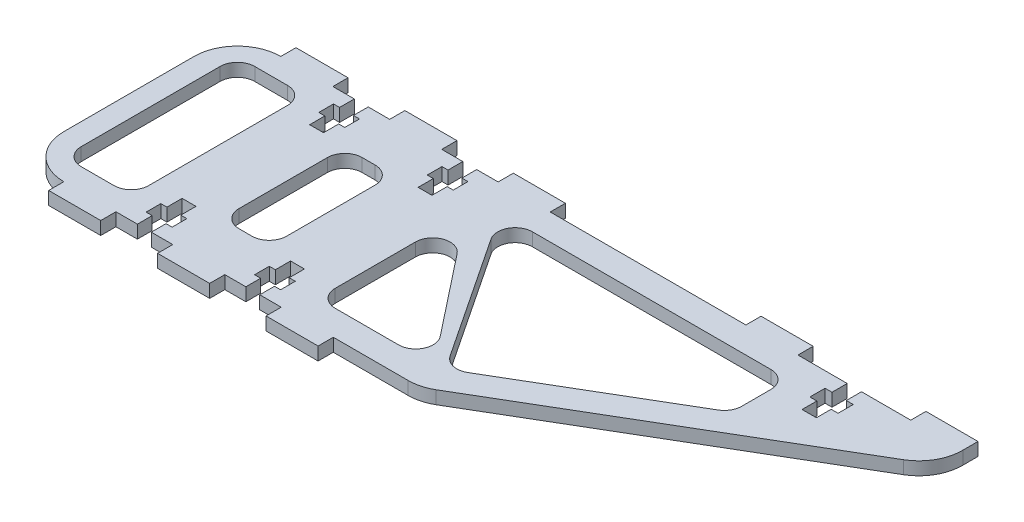
SolidWorks part; units mm, degrees
material "Thornel Mat VMA"
ref_plane "前视基准面" through (0, 0, 0) normal (0, 0, 1) x (1, 0, 0)
ref_plane "上视基准面" through (0, 0, 0) normal (0, 1, 0) x (1, 0, 0)
ref_plane "右视基准面" through (0, 0, 0) normal (1, 0, 0) x (0, 0, -1)
sketch "草图1" plane through (0, 0, 0) normal (0, 1, 0) x (1, 0, 0)
  line L0 (10, 0) -> (10, -3.5)
  line L1 (0, 0) -> (10, 0)
  line L2 (0, 0) -> (0, 50)
  line L3 (0, 50) -> (10, 50)
  line L4 (82.1, 0) -> (82.1, 50)
  line L5 (10, -3.5) -> (22, -3.5)
  line L6 (22, -3.5) -> (22, 0)
  line L7 (26.95, 0) -> (26.95, 3.4)
  line L8 (26.95, 3.4) -> (25.55, 3.4)
  line L9 (25.55, 3.4) -> (25.55, 6.8)
  line L10 (25.55, 6.8) -> (26.95, 6.8)
  line L11 (26.95, 6.8) -> (26.95, 10.3)
  line L12 (26.95, 10.3) -> (30.15, 10.3)
  line L13 (30.15, 10.3) -> (30.15, 6.8)
  line L14 (30.15, 6.8) -> (31.55, 6.8)
  line L15 (31.55, 6.8) -> (31.55, 3.4)
  line L16 (31.55, 3.4) -> (30.15, 3.4)
  line L17 (30.15, 3.4) -> (30.15, 0)
  line L18 (28.55, -0.9012) -> (28.55, 13.2859) construction
  line L19 (22, 0) -> (26.95, 0)
  line L20 (30.15, 0) -> (35.1, 0)
  line L21 (35.1, 0) -> (35.1, -3.5)
  line L22 (35.1, -3.5) -> (47.1, -3.5)
  line L23 (47.1, -3.5) -> (47.1, 0)
  line L24 (47.1, 0) -> (51.95, 0)
  line L25 (0, 25) -> (82.1, 25) construction
  line L26 (28.55, 50.9012) -> (28.55, 36.7141) construction
  line L27 (30.15, 46.6) -> (30.15, 50)
  line L28 (31.55, 46.6) -> (30.15, 46.6)
  line L29 (31.55, 43.2) -> (31.55, 46.6)
  line L30 (30.15, 43.2) -> (31.55, 43.2)
  line L31 (30.15, 39.7) -> (30.15, 43.2)
  line L32 (26.95, 39.7) -> (30.15, 39.7)
  line L33 (26.95, 43.2) -> (26.95, 39.7)
  line L34 (25.55, 43.2) -> (26.95, 43.2)
  line L35 (25.55, 46.6) -> (25.55, 43.2)
  line L36 (50.65, 3.4) -> (50.65, 6.8) [skipped]
  line L37 (50.65, 6.8) -> (52.05, 6.8) [skipped]
  line L38 (52.05, 6.8) -> (52.05, 10.3) [skipped]
  line L39 (56.65, 3.4) -> (55.25, 3.4) [skipped]
  line L40 (56.65, 6.8) -> (56.65, 3.4) [skipped]
  line L41 (55.25, 6.8) -> (56.65, 6.8) [skipped]
  line L42 (55.25, 10.3) -> (55.25, 6.8) [skipped]
  line L43 (52.05, 10.3) -> (55.25, 10.3) [skipped]
  line L44 (52.05, 0) -> (52.05, 3.4) [skipped]
  line L45 (55.25, 3.4) -> (55.25, 0) [skipped]
  line L46 (26.95, 46.6) -> (25.55, 46.6)
  line L47 (26.95, 50) -> (26.95, 46.6)
  line L48 (47.1, 53.5) -> (47.1, 50)
  line L49 (35.1, 53.5) -> (47.1, 53.5)
  line L50 (35.1, 50) -> (35.1, 53.5)
  line L51 (22, 53.5) -> (22, 50)
  line L52 (10, 53.5) -> (22, 53.5)
  line L53 (10, 50) -> (10, 53.5)
  line L54 (22, 50) -> (26.95, 50)
  line L55 (30.15, 50) -> (35.1, 50)
  line L56 (47.1, 50) -> (51.95, 50)
  line L57 (51.95, 0) -> (51.95, 3.4)
  line L58 (51.95, 3.4) -> (50.55, 3.4)
  line L59 (50.55, 3.4) -> (50.55, 6.8)
  line L60 (50.55, 6.8) -> (51.95, 6.8)
  line L61 (51.95, 6.8) -> (51.95, 10.3)
  line L62 (51.95, 10.3) -> (55.15, 10.3)
  line L63 (55.15, 10.3) -> (55.15, 6.8)
  line L64 (55.15, 6.8) -> (56.55, 6.8)
  line L65 (56.55, 6.8) -> (56.55, 3.4)
  line L66 (56.55, 3.4) -> (55.15, 3.4)
  line L67 (55.15, 3.4) -> (55.15, 0)
  line L68 (53.55, -0.9012) -> (53.55, 13.2859) construction
  line L69 (60.1, 0) -> (60.1, -3.5)
  line L70 (60.1, -3.5) -> (72.1, -3.5)
  line L71 (72.1, -3.5) -> (72.1, 0)
  line L72 (55.15, 46.6) -> (55.15, 50)
  line L73 (56.55, 46.6) -> (55.15, 46.6)
  line L74 (56.55, 43.2) -> (56.55, 46.6)
  line L75 (55.15, 43.2) -> (56.55, 43.2)
  line L76 (55.15, 39.7) -> (55.15, 43.2)
  line L77 (51.95, 39.7) -> (55.15, 39.7)
  line L78 (51.95, 43.2) -> (51.95, 39.7)
  line L79 (50.55, 43.2) -> (51.95, 43.2)
  line L80 (50.55, 46.6) -> (50.55, 43.2)
  line L81 (51.95, 46.6) -> (50.55, 46.6)
  line L82 (51.95, 50) -> (51.95, 46.6)
  line L83 (72.1, 53.5) -> (72.1, 50)
  line L84 (60.1, 53.5) -> (72.1, 53.5)
  line L85 (60.1, 50) -> (60.1, 53.5)
  line L86 (55.15, 50) -> (60.1, 50)
  line L87 (55.15, 0) -> (60.1, 0)
  line L88 (72.1, 0) -> (82.1, 0)
  line L89 (72.1, 50) -> (82.1, 50)
  line L90 (82.1, 0) -> (92.1, 0)
  line L91 (177.1, 50) -> (82.1, 50)
  line L92 (142.2, 50) -> (142.2, 30.5556) construction
  line L93 (155.2, 50) -> (167.2, 50)
  line L94 (155.2, 50) -> (155.2, 53.5)
  line L95 (155.2, 53.5) -> (167.2, 53.5)
  line L96 (167.2, 50) -> (167.2, 53.5)
  line L97 (129.2, 50) -> (117.2, 50)
  line L98 (129.2, 50) -> (129.2, 53.5)
  line L99 (129.2, 53.5) -> (117.2, 53.5)
  line L100 (117.2, 50) -> (117.2, 53.5)
  line L101 (53.55, 39.7) -> (53.55, 40) construction
  line L102 (92.1, 0) -> (177.1, 50)
  line L103 (140.55, 50) -> (140.55, 46.5)
  line L104 (140.55, 46.5) -> (138.95, 46.5)
  line L105 (138.95, 46.5) -> (138.95, 43)
  line L106 (138.95, 43) -> (140.55, 43)
  line L107 (140.55, 43) -> (140.55, 39.6)
  line L108 (140.55, 39.6) -> (143.85, 39.6)
  line L109 (143.85, 39.6) -> (143.85, 43)
  line L110 (143.85, 43) -> (145.45, 43)
  line L111 (145.45, 43) -> (145.45, 46.5)
  line L112 (145.45, 46.5) -> (143.85, 46.5)
  line L113 (143.85, 46.5) -> (143.85, 50)
  dimension "D1" = 3.5
  dimension "D2" = 12
  dimension "D3" = 10
  dimension "D4" = 4.95
  dimension "D5" = 3.2
  dimension "D6" = 3.4
  dimension "D7" = 3.4
  dimension "D8" = 3.5
  dimension "D9" = 6
  dimension "D10" = 50
  dimension "D11" = 10
  dimension "D13" = 4.95
  dimension "D14" = 2
  dimension "D16" = 25
  dimension "D17" = 12
  dimension "D18" = 12
  dimension "D19" = 3.5
  dimension "D20" = 3.5
  dimension "D21" = 9.9
  dimension "D22" = 95
  dimension "D23" = 50
  dimension "D24" = 25
  dimension "D25" = 10
  dimension "D26" = 3.3
  dimension "D27" = 3.5
  dimension "D28" = 3.5
  dimension "D29" = 3.4
  dimension "D30" = 6.5
  dimension "D12" = 2
  dimension "D15" = 2
extrude "凸台-拉伸1" add sketch "草图1" along normal blind 3
fillet "圆角1" radius 10 1 edges at (177.1, 1.5, -50)
fillet "圆角2" radius 10 3 edges at (92.1, 1.5, 0) (0, 1.5, -50) (0, 1.5, 0)
sketch "草图2" plane through (0, 0, 0) normal (0, -1, 0) x (1, 0, 0)
  line L0 (62.55, -6) -> (62.55, -44)
  line L1 (62.55, -44) -> (132.95, -44)
  line L2 (132.95, -44) -> (132.95, -30.9905)
  line L3 (132.95, -30.9905) -> (90.4662, -6)
  line L4 (90.4662, -6) -> (62.55, -6)
  line L5 (94.4471, -1.3807) -> (162.2707, -41.2769) construction
  line L6 (72.1, 0) -> (89.3769, 0) construction
  line L7 (56.55, -6.8) -> (56.55, -3.4) construction
  line L8 (72.1, -50) -> (117.2, -50) construction
  line L9 (138.95, -46.5) -> (138.95, -43) construction
  line L11 (35.55, -10.8) -> (46.55, -10.8)
  line L12 (35.55, -10.8) -> (35.55, -39.2)
  line L13 (35.55, -39.2) -> (46.55, -39.2)
  line L14 (46.55, -10.8) -> (46.55, -39.2)
  line L16 (31.55, -43.2) -> (31.55, -46.6) construction
  line L17 (50.55, -46.6) -> (50.55, -43.2) construction
  line L18 (30.15, -6.8) -> (31.55, -6.8) construction
  line L19 (30.15, -43.2) -> (31.55, -43.2) construction
  line L20 (0, -10) -> (0, -40) construction
  line L21 (5, -5) -> (20.55, -5)
  line L22 (5, -5) -> (5, -45)
  line L23 (5, -45) -> (20.55, -45)
  line L24 (20.55, -5) -> (20.55, -45)
  line L25 (22, 0) -> (26.95, 0) construction
  line L26 (22, -50) -> (26.95, -50) construction
  line L27 (25.55, -46.6) -> (25.55, -43.2) construction
  point P15 (138.95, -44.75)
  dimension "D1" = 6
  dimension "D2" = 6
  dimension "D3" = 6
  dimension "D4" = 6
  dimension "D5" = 6
  dimension "D6" = 4
  dimension "D7" = 4
  dimension "D8" = 4
  dimension "D9" = 4
  dimension "D10" = 5
  dimension "D11" = 5
  dimension "D12" = 5
  dimension "D13" = 5
extrude "切除-拉伸1" cut sketch "草图2" against normal through all
fillet "圆角3" radius 4 13 edges at (132.95, 1.5, -30.9905) (132.95, 1.5, -44) (90.4662, 1.5, -6) (62.55, 1.5, -6) (62.55, 1.5, -44) (35.55, 1.5, -39.2) (35.55, 1.5, -10.8) (46.55, 1.5, -10.8) (46.55, 1.5, -39.2) (20.55, 1.5, -45) (20.55, 1.5, -5) (5, 1.5, -5) (5, 1.5, -45)
sketch "草图3" plane through (0, 0, 0) normal (0, -1, 0) x (1, 0, 0)
  line L0 (62.55, -40) -> (89.3769, -6)
  line L1 (91.405, -6.5523) -> (66.55, -44)
  arc A0 (91.405, -6.5523) -> (89.3769, -6) centre (89.3769, -10) ccw construction
  arc A1 (91.405, -6.5523) -> (89.3769, -6) centre (89.3769, -10) ccw
  arc A2 (62.55, -40) -> (66.55, -44) centre (66.55, -40) ccw construction
  arc A3 (62.55, -40) -> (66.55, -44) centre (66.55, -40) ccw
extrude "凸台-拉伸2" add sketch "草图3" against normal blind 3
fillet "圆角4" radius 4 4 edges at (62.55, 1.5, -40) (66.55, 1.5, -44) (91.405, 1.5, -6.5523) (89.3769, 1.5, -6)
